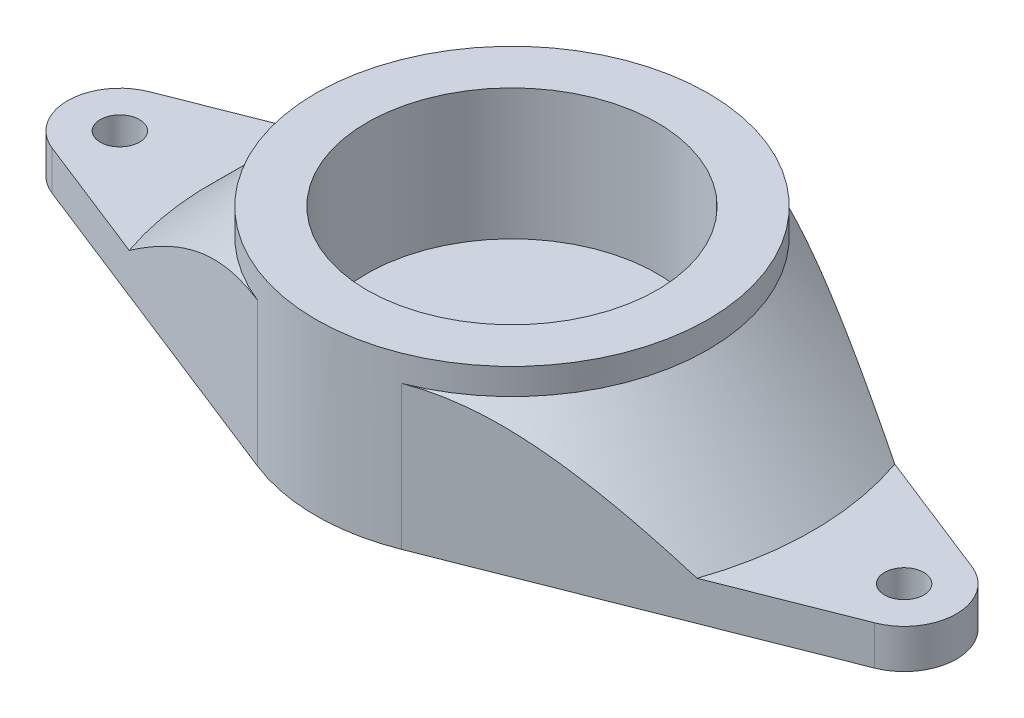
SolidWorks part; units mm, degrees
ref_plane "Alzado" through (0, 0, 0) normal (0, 0, 1) x (1, 0, 0)
ref_plane "Planta" through (0, 0, 0) normal (0, 1, 0) x (1, 0, 0)
ref_plane "Vista lateral" through (0, 0, 0) normal (1, 0, 0) x (0, 0, -1)
sketch "Croquis1" plane through (0, 0, 0) normal (0, 1, 0) x (1, 0, 0)
  line L0 (0, 0) -> (-30, 0)
  line L1 (0, 0) -> (30, 0)
  line L2 (-31.4667, 3.7214) -> (-5.5, 13.9553)
  line L3 (-31.4667, -3.7214) -> (-5.5, -13.9553)
  line L4 (0, 0) -> (0, -5.5042) construction
  line L5 (31.4667, -3.7214) -> (5.5, -13.9553)
  line L6 (31.4667, 3.7214) -> (5.5, 13.9553)
  circle A1 centre (0, 0) radius 11.1
  circle A2 centre (0, 0) radius 15
  circle A3 centre (-30, 0) radius 1.5
  circle A4 centre (30, 0) radius 1.5
  circle A5 centre (-30, 0) radius 4
  circle A6 centre (30, 0) radius 4
  dimension "D1" = 30
  dimension "D2" = 22.2
  dimension "D5" = 3
  dimension "D6" = 3
  dimension "D7" = 8
  dimension "D8" = 8
  dimension "D3" = 30
  dimension "D4" = 30
extrude "Saliente-Extruir1" add sketch "Croquis1" along normal blind 3
sketch "Croquis2" plane through (0, 3, 0) normal (0, 1, 0) x (1, 0, 0)
  line L0 (31.4667, -3.7214) -> (5.5, -13.9553) construction
  line L1 (-31.4667, -3.7214) -> (-5.5, -13.9553) construction
  line L2 (-31.4667, 3.7214) -> (-5.5, 13.9553) construction
  line L3 (0, 0) -> (-30, 0) construction
  line L4 (0, 0) -> (30, 0) construction
  line L5 (31.4667, 3.7214) -> (5.5, 13.9553) construction
  line L6 (31.4667, -3.7214) -> (5.5, -13.9553)
  line L7 (-31.4667, -3.7214) -> (-5.5, -13.9553)
  line L8 (-31.4667, 3.7214) -> (-5.5, 13.9553)
  line L9 (0, 0) -> (-30, 0)
  line L10 (0, 0) -> (30, 0)
  line L11 (31.4667, 3.7214) -> (5.5, 13.9553)
  circle A1 centre (30, 0) radius 4
  circle A2 centre (30, 0) radius 4
  circle A3 centre (-30, 0) radius 4
  circle A4 centre (-30, 0) radius 4
  circle A5 centre (30, 0) radius 1.5
  circle A6 centre (30, 0) radius 1.5
  circle A7 centre (-30, 0) radius 1.5
  circle A8 centre (-30, 0) radius 1.5
  circle A9 centre (0, 0) radius 15
  circle A10 centre (0, 0) radius 15
  circle A11 centre (0, 0) radius 11.1
  circle A12 centre (0, 0) radius 11.1
  dimension "D1" = 0
  dimension "D2" = 0
  dimension "D3" = 0
  dimension "D4" = 0
  dimension "D5" = 0
  dimension "D6" = 0
extrude "Saliente-Extruir2" add sketch "Croquis2" along normal blind 10 contours A10 | A12
chamfer "Chaflán1" distance 8 angle 45 1 edges at (15, 3, 0)
